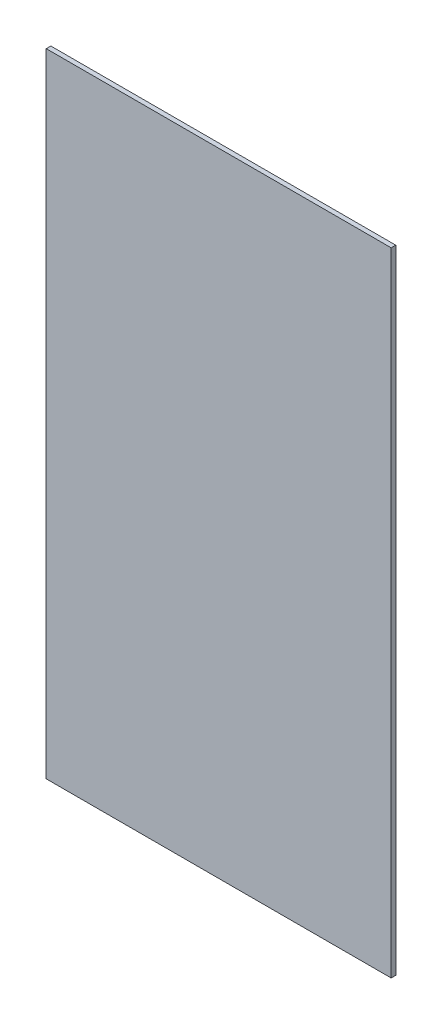
SolidWorks part; units mm, degrees
ref_plane "Front Plane" through (0, 0, 0) normal (0, 0, 1) x (1, 0, 0)
ref_plane "Top Plane" through (0, 0, 0) normal (0, 1, 0) x (1, 0, 0)
ref_plane "Right Plane" through (0, 0, 0) normal (1, 0, 0) x (0, 0, -1)
sketch "Sketch1" plane through (0, 0, 0) normal (0, 0, 1) x (1, 0, 0)
  line L1 (-30.5262, 77.2604) -> (29.4738, 77.2604)
  line L2 (-30.5262, 77.2604) -> (-30.5262, -32.7396)
  line L3 (-30.5262, -32.7396) -> (29.4738, -32.7396)
  line L4 (29.4738, 77.2604) -> (29.4738, -32.7396)
  dimension "D1" = 110
  dimension "D2" = 60
extrude "Boss-Extrude1" add sketch "Sketch1" along normal blind 0.8
